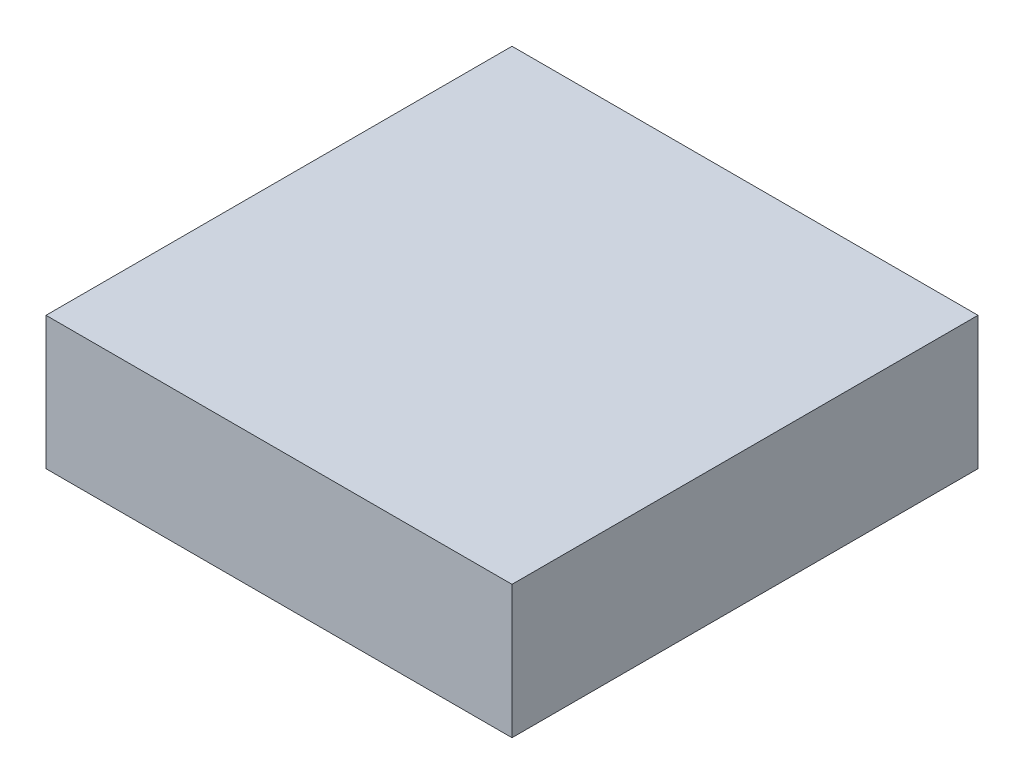
SolidWorks part; units mm, degrees
ref_plane "Alzado" through (0, 0, 0) normal (0, 0, 1) x (1, 0, 0)
ref_plane "Planta" through (0, 0, 0) normal (0, 1, 0) x (1, 0, 0)
ref_plane "Vista lateral" through (0, 0, 0) normal (1, 0, 0) x (0, 0, -1)
sketch "Croquis1" plane through (0, 0, 0) normal (0, 1, 0) x (1, 0, 0)
  line L1 (-49.1, 49.1) -> (49.1, 49.1)
  line L2 (-49.1, 49.1) -> (-49.1, -49.1)
  line L3 (-49.1, -49.1) -> (49.1, -49.1)
  line L4 (49.1, 49.1) -> (49.1, -49.1)
  point P4 (0, 49.1)
  point P6 (-49.1, 0)
  dimension "D1" = 98.2
  dimension "D2" = 98.2
extrude "Saliente-Extruir2" add sketch "Croquis1" against normal blind 28
sketch "Croquis2" plane through (0, -28, 0) normal (0, -1, 0) x (1, 0, 0)
  line L1 (-45.1, 45.1) -> (45.1, 45.1)
  line L2 (-45.1, 45.1) -> (-45.1, -45.1)
  line L3 (-45.1, -45.1) -> (45.1, -45.1)
  line L4 (45.1, 45.1) -> (45.1, -45.1)
  point P4 (0, 45.1)
  point P6 (-45.1, 0)
  dimension "D1" = 90.2
  dimension "D2" = 90.2
extrude "Cortar-Extruir1" cut sketch "Croquis2" against normal blind 24
sketch "Croquis3" plane through (0, -4, 0) normal (0, -1, 0) x (1, 0, 0)
  line L1 (45.1, 45.1) -> (-45.1, 45.1) construction
  line L4 (13, 13.6) -> (-13, 13.6)
  line L5 (-13, -23.9) -> (-13, 13.6)
  line L6 (-13, 13.6) -> (-13, 11.1)
  line L7 (-13, 11.1) -> (-15.6, 11.1) construction
  line L8 (-13, -23.9) -> (-18.5436, -23.9) construction
  line L10 (-13, -23.9) -> (-15.6, -23.9)
  line L11 (-13, -23.9) -> (-13, 11.1)
  line L12 (-13, 11.1) -> (-15.6, 11.1)
  line L13 (-15.6, -23.9) -> (-15.6, 11.1)
  line L15 (13, 11.1) -> (13, -23.9)
  point P7 (0, 13.6)
  dimension "D1" = 26
  dimension "D2" = 34
  dimension "D3" = 2.5
  dimension "D4" = 2.6
  dimension "D8" = 2.5
extrude "Saliente-Extruir3" add sketch "Croquis3" along normal blind 22 contours L13 L10 L5 L12 region at (-14.3, -4, -6.4)
sketch "Croquis5" plane through (0, -4, 0) normal (0, -1, 0) x (1, 0, 0)
  line L2 (-13, 11.1) -> (-13, -36.0115)
  line L4 (14.19, 11.1) -> (14.19, -36.0115)
  line L5 (14.19, 11.1) -> (16.79, 11.1)
  line L6 (14.19, 11.1) -> (14.19, -23.9)
  line L7 (14.19, -23.9) -> (16.79, -23.9)
  line L8 (16.79, 11.1) -> (16.79, -23.9)
  dimension "D1" = 27.19
  dimension "D2" = 35
  dimension "D3" = 2.6
extrude "Saliente-Extruir4" add sketch "Croquis5" along normal blind 22 contours L8 L5 L4 L6 L7 region at (15.49, -4, -6.4)
